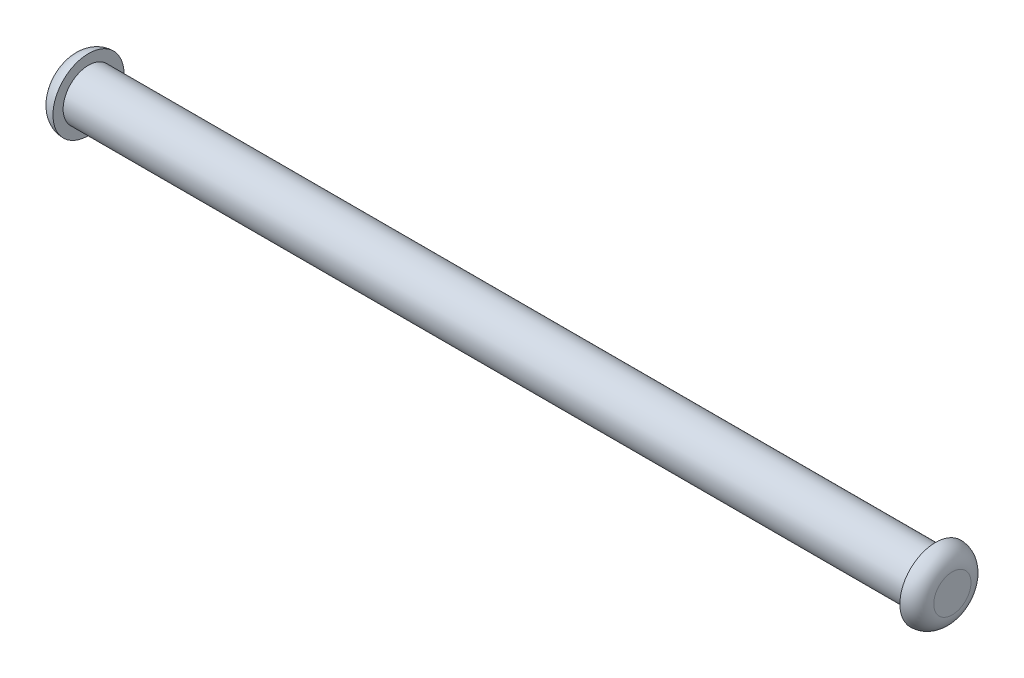
SolidWorks part; units mm, degrees
ref_plane "Front Plane" through (0, 0, 0) normal (0, 0, 1) x (1, 0, 0)
ref_plane "Top Plane" through (0, 0, 0) normal (0, 1, 0) x (1, 0, 0)
ref_plane "Right Plane" through (0, 0, 0) normal (1, 0, 0) x (0, 0, -1)
sketch "Sketch1" plane through (0, 0, 0) normal (1, 0, 0) x (0, 0, -1)
  circle A0 centre (0, 0) radius 2.1
  dimension "D1" = 4.2
extrude "Boss-Extrude1" add sketch "Sketch1" along normal blind 1
sketch "Sketch2" plane through (1, 0, 0) normal (1, 0, 0) x (0, 0, -1)
  circle A0 centre (0, 0) radius 1.5
  dimension "D1" = 3
extrude "Boss-Extrude2" add sketch "Sketch2" along normal blind 50
sketch "Sketch3" plane through (51, 0, 0) normal (1, 0, 0) x (0, 0, -1)
  circle A0 centre (0, 0) radius 2.1
  dimension "D1" = 4.2
extrude "Boss-Extrude3" add sketch "Sketch3" along normal blind 1
fillet "Fillet1" radius 1 2 edges at (52, 0, -2.1) (0, 0, -2.1)
